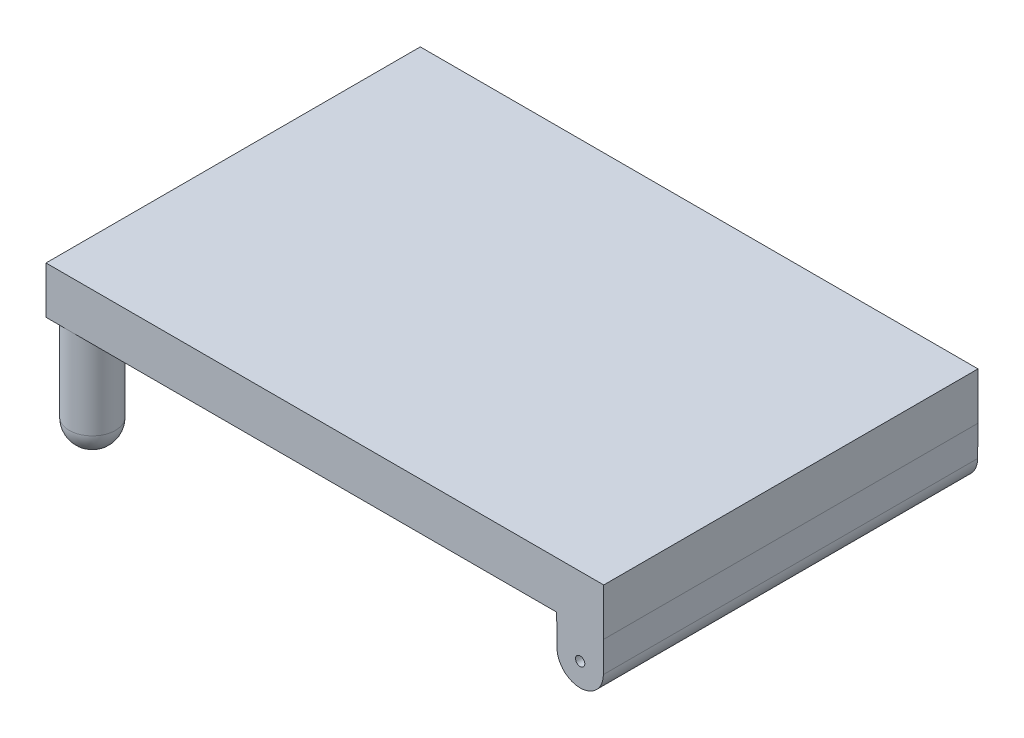
SolidWorks part; units mm, degrees
ref_plane "Front Plane" through (0, 0, 0) normal (0, 0, 1) x (1, 0, 0)
ref_plane "Top Plane" through (0, 0, 0) normal (0, 1, 0) x (1, 0, 0)
ref_plane "Right Plane" through (0, 0, 0) normal (1, 0, 0) x (0, 0, -1)
sketch "Sketch1" plane through (0, 0, 0) normal (0, 1, 0) x (1, 0, 0)
  line L1 (150.5, -101) -> (-150.5, -101)
  line L2 (150.5, -101) -> (150.5, 101)
  line L3 (150.5, 101) -> (-150.5, 101)
  line L4 (-150.5, -101) -> (-150.5, 101)
  line L5 (150.5, -101) -> (-150.5, 101) construction
  line L6 (150.5, 101) -> (-150.5, -101) construction
  point P0 (0, 0)
  dimension "D1" = 301
  dimension "D2" = 202
extrude "Boss-Extrude1" add sketch "Sketch1" along normal blind 60
sketch "Sketch2" plane through (0, 0, 101) normal (0, 0, 1) x (1, 0, 0)
  line L0 (-150.5, 60) -> (150.5, 60) construction
  line L1 (150.5, 60) -> (150.5, 0) construction
  circle A0 centre (137.8, 18) radius 2.5
  dimension "D1" = 5
  dimension "D2" = 42
  dimension "D3" = 12.7
sketch "Sketch4" plane through (0, 0, 101) normal (0, 0, 1) x (1, 0, 0)
  line L0 (137.8, 18) -> (137.8, 60) construction
  line L1 (125.1, 60) -> (150.5, 60)
  line L2 (125.1, 60) -> (125.1, 34.6)
  line L3 (125.1, 34.6) -> (150.5, 34.6)
  line L4 (150.5, 60) -> (150.5, 34.6)
  line L5 (-150.5, 60) -> (150.5, 60) construction
  line L6 (125.3, 18) -> (125.1, 34.6)
  line L7 (150.3, 18) -> (150.5, 34.6)
  line L8 (-150.5, 60) -> (125.1, 60)
  line L9 (-150.5, 60) -> (-150.5, 34.6)
  line L10 (-150.5, 34.6) -> (125.1, 34.6)
  line L11 (125.1, 60) -> (125.1, 34.6)
  circle A0 centre (137.8, 18) radius 12.5
  point P16 (0, 0)
  point P17 (0, 0)
  line M12 (-150.5, 0) -> (150.5, 0)
  line M13 (150.5, 0) -> (150.5, 60)
  line M15 (-150.5, 60) -> (-150.5, 0)
  dimension "D1" = 25
  dimension "D2" = 25.4
  dimension "D3" = 25.4
  dimension "D4" = 25.4
extrude "Cut-Extrude1" cut sketch "Sketch4" against normal through all contours A0 L6 L10 L7 M15 M12 M13 region at (-9.3803, 17.0289, 101)
sketch "Sketch5" plane through (0, 34.6, 0) normal (0, -1, 0) x (1, 0, 0)
  line L0 (-138, 88.5) -> (-138, -88.5) construction
  line L1 (-150.5, -101) -> (-150.5, 101) construction
  line L2 (-150.5, -101) -> (125.1, -101) construction
  line L3 (-150.5, 101) -> (125.1, 101) construction
  circle A0 centre (-138, 88.5) radius 12.5
  circle A1 centre (-138, -88.5) radius 12.5
  dimension "D1" = 25
extrude "Boss-Extrude2" add sketch "Sketch5" along normal blind 59.1
fillet "Fillet1" radius 12.5 2 edges at (-138, -24.5, -101) (-138, -24.5, 76)
extrude "Cut-Extrude2" cut sketch "Sketch2" against normal through all contours A0
